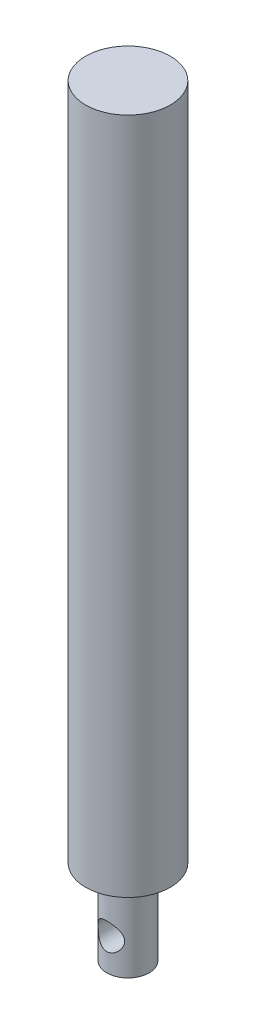
SolidWorks part; units mm, degrees
material "Plain Carbon Steel"
ref_plane "Front Plane" through (0, 0, 0) normal (0, 0, 1) x (1, 0, 0)
ref_plane "Top Plane" through (0, 0, 0) normal (0, 1, 0) x (1, 0, 0)
ref_plane "Right Plane" through (0, 0, 0) normal (1, 0, 0) x (0, 0, -1)
sketch "Sketch1" plane through (0, 0, 0) normal (0, 1, 0) x (1, 0, 0)
  circle A0 centre (0, 0) radius 6.35
  circle A1 centre (0, 0) radius 12.7
  dimension "D1" = 12.7
  dimension "D2" = 25.4
extrude "Boss-Extrude1" add sketch "Sketch1" along normal blind 203.2 contours A0 | A1 A0 region at (0, 0, 0) region at (-12.3408, 0, 0)
extrude "Boss-Extrude2" add sketch "Sketch1<3>" against normal blind 25.4 contours A0 region at (0, 0, 0)
sketch "Sketch1<3>" plane through (0, 0, 0) normal (0, 1, 0) x (1, 0, 0) same geometry as "Sketch1"
sketch "Sketch3" plane through (0, 0, 0) normal (0, 0, 1) x (1, 0, 0)
  line L0 (-6.35, -25.4) -> (6.35, -25.4) construction
  circle A0 centre (0, -15.875) radius 3.9688
  dimension "D1" = 7.9375
  dimension "D2" = 9.525
extrude "Cut-Extrude2" cut sketch "Sketch3" against normal through all both and the other way through all
